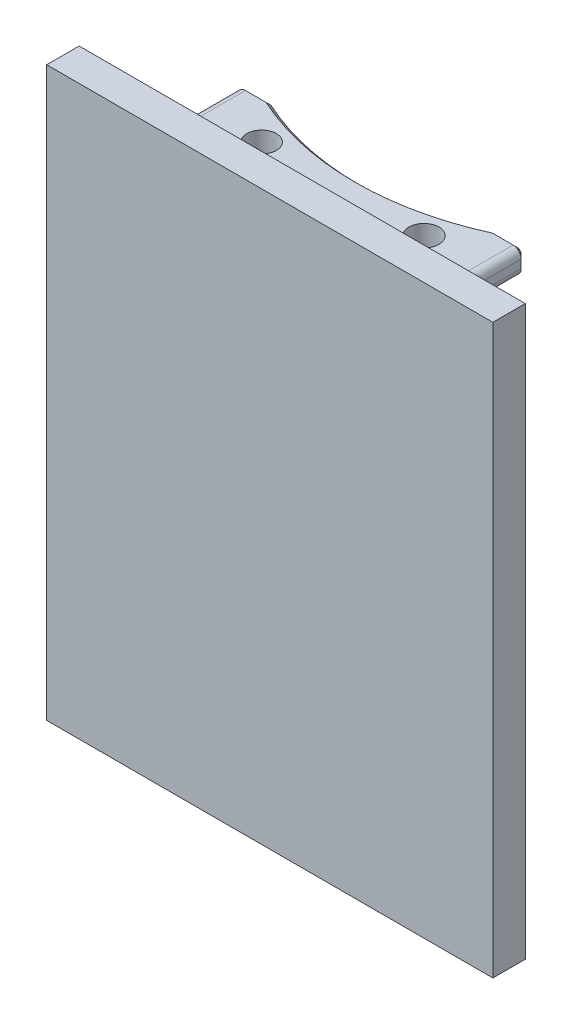
SolidWorks part; units mm, degrees
ref_plane "Front Plane" through (0, 0, 0) normal (0, 0, 1) x (1, 0, 0)
ref_plane "Top Plane" through (0, 0, 0) normal (0, 1, 0) x (1, 0, 0)
ref_plane "Right Plane" through (0, 0, 0) normal (1, 0, 0) x (0, 0, -1)
sketch "Sketch1" plane through (0, 0, 0) normal (0, 0, 1) x (1, 0, 0)
  line L1 (27.5, -35) -> (-27.5, -35)
  line L2 (27.5, -35) -> (27.5, 35)
  line L3 (27.5, 35) -> (-27.5, 35)
  line L4 (-27.5, -35) -> (-27.5, 35)
  line L5 (27.5, -35) -> (-27.5, 35) construction
  line L6 (27.5, 35) -> (-27.5, -35) construction
  point P0 (0, 0)
  dimension "D1" = 55
  dimension "D2" = 70
extrude "Boss-Extrude1" add sketch "Sketch1" along normal blind 4
sketch "Sketch2" plane through (0, 0, 0) normal (0, 0, -1) x (-1, 0, 0)
  line L0 (0, 0) -> (0, 55.6129) construction
  line L1 (-17.5, 31) -> (17.5, 31) construction
  line L3 (-17.5, 18) -> (17.5, 18) construction
  line L5 (-16.5, 28) -> (16.5, 28)
  line L6 (-17.5, 29) -> (-17.5, 30)
  line L7 (-16.5, 31) -> (16.5, 31)
  line L8 (17.5, 29) -> (17.5, 30)
  line L9 (-16.5, 18) -> (16.5, 18)
  line L10 (-17.5, 17) -> (-17.5, 16)
  line L11 (-16.5, 15) -> (16.5, 15)
  line L12 (17.5, 17) -> (17.5, 16)
  line L13 (0, 0) -> (53.7702, 0) construction
  line L14 (-16.5, -31) -> (16.5, -31)
  line L15 (17.5, -29) -> (17.5, -30)
  line L16 (-16.5, -28) -> (16.5, -28)
  line L17 (-17.5, -29) -> (-17.5, -30)
  line L18 (-16.5, -15) -> (16.5, -15)
  line L19 (17.5, -17) -> (17.5, -16)
  line L20 (-16.5, -18) -> (16.5, -18)
  line L21 (-17.5, -17) -> (-17.5, -16)
  arc A0 (-16.5, 18) -> (-17.5, 17) centre (-16.5, 17) ccw
  arc A1 (-17.5, 16) -> (-16.5, 15) centre (-16.5, 16) ccw
  arc A2 (16.5, 15) -> (17.5, 16) centre (16.5, 16) ccw
  arc A3 (17.5, 17) -> (16.5, 18) centre (16.5, 17) ccw
  arc A4 (16.5, 31) -> (17.5, 30) centre (16.5, 30) cw
  arc A5 (16.5, 28) -> (17.5, 29) centre (16.5, 29) ccw
  arc A6 (-16.5, 28) -> (-17.5, 29) centre (-16.5, 29) cw
  arc A7 (-16.5, 31) -> (-17.5, 30) centre (-16.5, 30) ccw
  arc A8 (16.5, -31) -> (17.5, -30) centre (16.5, -30) ccw
  arc A9 (16.5, -28) -> (17.5, -29) centre (16.5, -29) cw
  arc A10 (-16.5, -28) -> (-17.5, -29) centre (-16.5, -29) ccw
  arc A11 (-16.5, -31) -> (-17.5, -30) centre (-16.5, -30) cw
  arc A12 (16.5, -15) -> (17.5, -16) centre (16.5, -16) cw
  arc A13 (17.5, -17) -> (16.5, -18) centre (16.5, -17) cw
  arc A14 (-16.5, -18) -> (-17.5, -17) centre (-16.5, -17) cw
  arc A15 (-17.5, -16) -> (-16.5, -15) centre (-16.5, -16) cw
  point P18 (17.5, 15)
  dimension "D4" = 1
  dimension "D1" = 10
  dimension "D2" = 3
  dimension "D3" = 35
  dimension "D5" = 30
extrude "Boss-Extrude2" add sketch "Sketch2" along normal blind 10
sketch "Sketch3" plane through (0, -31, 0) normal (0, -1, 0) x (1, 0, 0)
  line L0 (-10, -5) -> (10, -5) construction
  line L1 (0, -10) -> (0, 0) construction
  line L2 (16.5, -10) -> (-16.5, -10) construction
  line L3 (-27.5, 0) -> (27.5, 0) construction
  circle A0 centre (-10, -5) radius 1.8077
  circle A1 centre (10, -5) radius 1.85
  point P7 (0, -5)
  point P10 (-12.5, -3.5113)
  dimension "D1" = 3.7
  dimension "D2" = 20
  dimension "D3" = 5
extrude "Cut-Extrude1" cut sketch "Sketch3" against normal through all both and the other way through all
sketch "Sketch4" plane through (0, -31, 0) normal (0, -1, 0) x (1, 0, 0)
  line L1 (0, 0) -> (0, -13.2973) construction
  circle A0 centre (10, -5) radius 2.1
  circle A1 centre (10, -5) radius 1.85 construction
  circle A2 centre (-10, -5) radius 2.1
  point P4 (0, 0)
  dimension "D1" = 4.2
extrude "Cut-Extrude2" cut sketch "Sketch4" against normal up to surface (3 mm away) and the other way through all up to face at (-10, -28, -6.8077)
extrude "Cut-Extrude3" cut sketch "Sketch4<2>" along direction (0, -1, 0) on the side against the normal up to surface (49 mm away) from surface up to face at (-10, 18, -6.8077) starting at face at (-10, 15, -3.1923)
sketch "Sketch4<2>" plane through (0, -31, 0) normal (0, -1, 0) x (1, 0, 0) same geometry as "Sketch4"
chamfer "Chamfer1" distance 0.5 angle 45 32 edges at (0, -31, -10) (17.2071, -30.7071, -10) (17.5, -29.5, -10) (17.2071, -28.2929, -10) (0, -28, -10) (-17.2071, -28.2929, -10) (-17.5, -29.5, -10) (-17.2071, -30.7071, -10) (-17.5, -16.5, -10) (-17.2071, -17.7071, -10) (0, -18, -10) (17.2071, -17.7071, -10) (17.5, -16.5, -10) (17.2071, -15.2929, -10) (0, -15, -10) (-17.2071, -15.2929, -10) (-17.5, 29.5, -10) (-17.2071, 28.2929, -10) (0, 28, -10) (17.2071, 28.2929, -10) (17.5, 29.5, -10) (17.2071, 30.7071, -10) (0, 31, -10) (-17.2071, 30.7071, -10) (0, 18, -10) (-17.2071, 17.7071, -10) (-17.5, 16.5, -10) (-17.2071, 15.2929, -10) (0, 15, -10) (17.2071, 15.2929, -10) (17.5, 16.5, -10) (17.2071, 17.7071, -10)
sketch "Sketch5" plane through (0, 31, 0) normal (0, 1, 0) x (1, 0, 0)
  circle A0 centre (0, 40) radius 33.04
extrude "Cut-Extrude4" cut sketch "Sketch5" against normal up to surface (62 mm away) up to face at (10, -31, -2.9)
chamfer "Chamfer2" distance 0.5 angle 45 8 edges at (0, -31, -6.96) (0, -28, -6.96) (0, -18, -6.96) (0, -15, -6.96) (0, 15, -6.96) (0, 18, -6.96) (0, 28, -6.96) (0, 31, -6.96)
